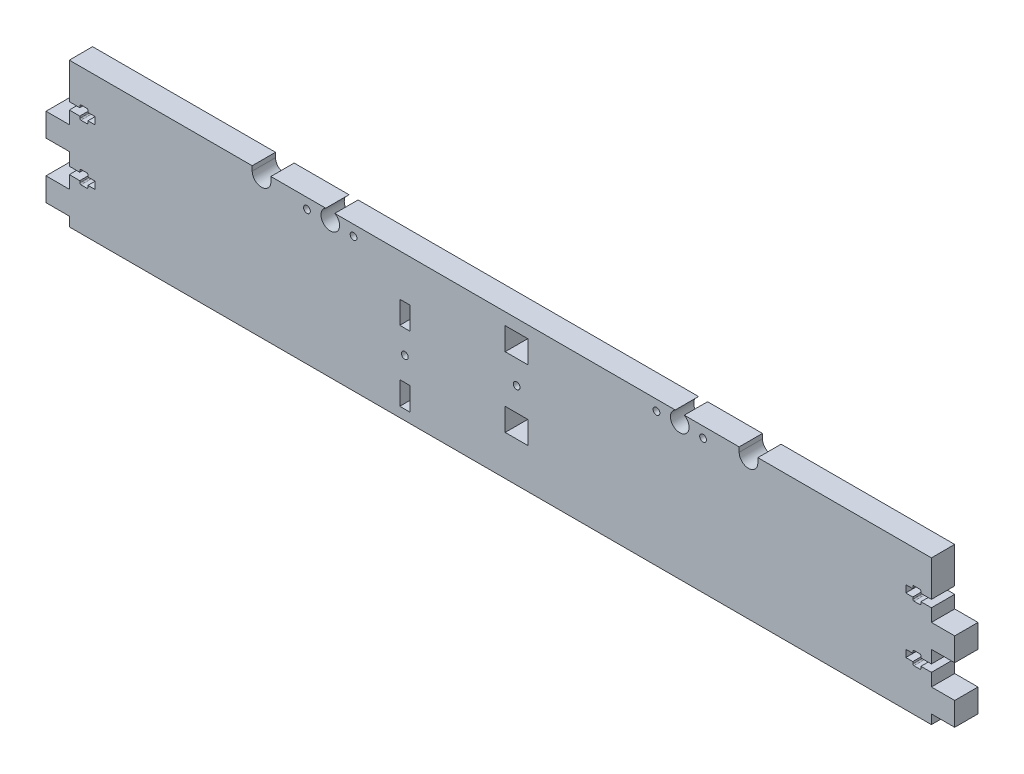
SolidWorks part; units mm, degrees
ref_plane "Front Plane" through (0, 0, 0) normal (0, 0, 1) x (1, 0, 0)
ref_plane "Top Plane" through (0, 0, 0) normal (0, 1, 0) x (1, 0, 0)
ref_plane "Right Plane" through (0, 0, 0) normal (1, 0, 0) x (0, 0, -1)
sketch "Sketch1" plane through (0, 0, 0) normal (0, 0, 1) x (1, 0, 0)
  line L0 (0, 0) -> (-185, 0)
  line L1 (-185, 0) -> (-185, -62) construction
  line L2 (0, -62) -> (-185, -62)
  line L3 (-185, -62) -> (-185, -58)
  line L4 (-185, -58) -> (-195, -58)
  line L5 (-195, -58) -> (-195, -48)
  line L6 (-195, -48) -> (-185, -48)
  line L7 (-185, -48) -> (-185, -34)
  line L8 (-185, -34) -> (-195, -34)
  line L9 (-195, -34) -> (-195, -24)
  line L10 (-195, -24) -> (-185, -24)
  line L11 (0, -62) -> (0, 0)
  line L12 (-185, -24) -> (-185, 0)
  line L13 (-195, -58) -> (-195, -24) construction
  line L14 (-195, -29) -> (-185, -29) construction
  line L15 (-195, -53) -> (-185, -53) construction
  dimension "D1" = 185
  dimension "D2" = 10
  dimension "D3" = 10
  dimension "D4" = 10
  dimension "D5" = 24
  dimension "D6" = 29
  dimension "D7" = 62
extrude "MainBody" add sketch "Sketch1" along normal blind 10
sketch "Sketch3" plane through (0, 0, 10) normal (0, 0, 1) x (1, 0, 0)
  line L0 (-185, -17) -> (-174, -17) construction
  line L1 (-185, 0) -> (-185, -24) construction
  line L2 (-185, -18.55) -> (-180.5, -18.55)
  line L3 (-180.5, -18.55) -> (-180.5, -19.35)
  line L4 (-180, -19.85) -> (-177.5, -19.85)
  line L5 (-177, -19.35) -> (-177, -18.55)
  line L6 (-177, -18.55) -> (-174, -18.55)
  line L7 (-174, -18.55) -> (-174, -15.45)
  line L8 (-180.5, -18.55) -> (-177, -18.55) construction
  line L9 (-195, -24) -> (-195, -34) construction
  line L10 (-180.5, -15.45) -> (-177, -15.45) construction
  line L11 (-177, -15.45) -> (-174, -15.45)
  line L12 (-177, -14.65) -> (-177, -15.45)
  line L13 (-180, -14.15) -> (-177.5, -14.15)
  line L14 (-180.5, -15.45) -> (-180.5, -14.65)
  line L15 (-185, -15.45) -> (-180.5, -15.45)
  line L16 (-185, -18.55) -> (-185, -15.45)
  line L17 (-185, -24) -> (-185, -34) construction
  line L19 (-195, -24) -> (-195, -34) construction
  line L20 (-195, -29) -> (-185, -29) construction
  line L21 (-180.5, -42.55) -> (-177, -42.55) construction
  line L22 (-180.5, -39.45) -> (-177, -39.45) construction
  line L23 (-185, -41) -> (-174, -41) construction
  line L24 (-185, -39.45) -> (-185, -42.55)
  line L25 (-185, -42.55) -> (-180.5, -42.55)
  line L26 (-180.5, -42.55) -> (-180.5, -43.35)
  line L27 (-180, -43.85) -> (-177.5, -43.85)
  line L28 (-177, -43.35) -> (-177, -42.55)
  line L29 (-177, -42.55) -> (-174, -42.55)
  line L30 (-174, -39.45) -> (-174, -42.55)
  line L31 (-177, -39.45) -> (-174, -39.45)
  line L32 (-177, -38.65) -> (-177, -39.45)
  line L33 (-180, -38.15) -> (-177.5, -38.15)
  line L34 (-180.5, -39.45) -> (-180.5, -38.65)
  line L35 (-185, -39.45) -> (-180.5, -39.45)
  line L36 (-180.5, -15.45) -> (-177, -15.45) construction
  arc A0 (-177.5, -19.85) -> (-177, -19.35) centre (-177.5, -19.35) ccw
  arc A1 (-180.5, -19.35) -> (-180, -19.85) centre (-180, -19.35) ccw
  arc A2 (-180.5, -14.65) -> (-180, -14.15) centre (-180, -14.65) cw
  arc A3 (-177.5, -14.15) -> (-177, -14.65) centre (-177.5, -14.65) cw
  arc A4 (-177.5, -43.85) -> (-177, -43.35) centre (-177.5, -43.35) ccw
  arc A5 (-180.5, -43.35) -> (-180, -43.85) centre (-180, -43.35) ccw
  arc A6 (-180.5, -38.65) -> (-180, -38.15) centre (-180, -38.65) cw
  arc A7 (-177.5, -38.15) -> (-177, -38.65) centre (-177.5, -38.65) cw
  point P6 (-195, -29)
  point P15 (-177, -19.85)
  point P18 (-180.5, -19.85)
  point P29 (-180.5, -14.15)
  point P30 (-177, -14.15)
  point P62 (-177, -43.85)
  point P63 (-180.5, -43.85)
  point P64 (-180.5, -38.15)
  point P65 (-177, -38.15)
  dimension "D2" = 8
  dimension "D7" = 0.5
  dimension "D1" = 11
  dimension "D3" = 1.55
  dimension "D4" = 2.85
  dimension "D5" = 12
  dimension "D6" = 3.5
extrude "ScrewCutouts" cut sketch "Sketch3" against normal through all
mirror "Mirror1" about plane through (0, 0, 0) normal (1, 0, 0) of "ScrewCutouts", "MainBody"
sketch "Sketch2" plane through (0, 0, 10) normal (0, 0, 1) x (1, 0, 0)
  line L0 (0, 0) -> (0, -62) construction
  line L1 (-185, -62) -> (185, -62) construction
  line L2 (2, 0) -> (2, -62) construction
  line L3 (185, 0) -> (-185, 0) construction
  line L4 (-63, -4.5) -> (-83, -4.5) construction
  line L5 (-73, -7.5) -> (-73, 0.5) construction
  line L6 (77, -7.5) -> (77, 0.5) construction
  line L7 (67, -4.5) -> (87, -4.5) construction
  circle A0 centre (-73, -3.5) radius 4
  circle A1 centre (-83, -4.5) radius 1.45
  circle A2 centre (-63, -4.5) radius 1.45
  circle A3 centre (67, -4.5) radius 1.45
  circle A4 centre (87, -4.5) radius 1.45
  circle A5 centre (77, -3.5) radius 4
  dimension "D1" = 2.9
  dimension "D2" = 8
  dimension "D4" = 3.5
  dimension "D5" = 75
  dimension "D6" = 2
  dimension "D3" = 10
  dimension "D7" = 1
extrude "RodCutouts" cut sketch "Sketch2" against normal through all
sketch "Sketch4" plane through (0, 0, 10) normal (0, 0, 1) x (1, 0, 0)
  line L0 (77, -3.5) -> (-73, -3.5) construction
  line L1 (2, -3.5) -> (2, -62) construction
  line L2 (-185, -62) -> (185, -62) construction
  line L3 (7, -44.85) -> (7, -5.15) construction
  line L4 (75.0635, 0) -> (-71.0635, 0) construction
  line L5 (7, -10) -> (7, -40) construction
  line L6 (2.075, -5.15) -> (11.925, -5.15)
  line L7 (2.075, -5.15) -> (2.075, -14.85)
  line L8 (2.075, -14.85) -> (11.925, -14.85)
  line L9 (11.925, -5.15) -> (11.925, -14.85)
  line L10 (2.075, -5.15) -> (11.925, -14.85) construction
  line L11 (2.075, -14.85) -> (11.925, -5.15) construction
  line L12 (2.075, -35.15) -> (11.925, -35.15)
  line L13 (2.075, -35.15) -> (2.075, -44.85)
  line L14 (2.075, -44.85) -> (11.925, -44.85)
  line L15 (11.925, -35.15) -> (11.925, -44.85)
  line L16 (2.075, -35.15) -> (11.925, -44.85) construction
  line L17 (2.075, -44.85) -> (11.925, -35.15) construction
  circle A0 centre (7, -25) radius 1.45
  point P12 (7, -10)
  point P17 (7, -40)
  dimension "D8" = 2.9
  dimension "D1" = 9.85
  dimension "D2" = 9.7
  dimension "D3" = 9.85
  dimension "D4" = 9.7
  dimension "D5" = 30
  dimension "D6" = 10
  dimension "D7" = 5
extrude "Cut-Extrude3" cut sketch "Sketch4" against normal through all
sketch "Sketch5" plane through (0, 0, 10) normal (0, 0, 1) x (1, 0, 0)
  line L0 (-41, 0) -> (-41, -62) construction
  line L1 (-74.9365, 0) -> (-185, 0) construction
  line L2 (-185, -62) -> (185, -62) construction
  line L3 (-43.175, -27.65) -> (-43.175, -47.85) construction
  line L4 (-43.175, -17.95) -> (-38.825, -17.95)
  line L5 (-43.175, -17.95) -> (-43.175, -27.65)
  line L6 (-43.175, -27.65) -> (-38.825, -27.65)
  line L7 (-38.825, -17.95) -> (-38.825, -27.65)
  line L8 (-43.175, -17.95) -> (-38.825, -27.65) construction
  line L9 (-43.175, -27.65) -> (-38.825, -17.95) construction
  line L10 (-43.175, -47.85) -> (-38.825, -47.85)
  line L11 (-43.175, -47.85) -> (-43.175, -57.75)
  line L12 (-43.175, -57.75) -> (-38.825, -57.75)
  line L13 (-38.825, -47.85) -> (-38.825, -57.75)
  line L14 (-43.175, -47.85) -> (-38.825, -57.75) construction
  line L15 (-43.175, -57.75) -> (-38.825, -47.85) construction
  line L16 (-38.825, -47.85) -> (-38.825, -27.65) construction
  line L17 (-43.175, -37.75) -> (-38.825, -37.75) construction
  line L18 (-73, -3.5) -> (77, -3.5) construction
  line L19 (2, -3.5) -> (2, -62) construction
  line L20 (2, -32.75) -> (-195, -32.75) construction
  line L21 (-195, -24) -> (-195, -34) construction
  line L22 (-34.625, 8.9944) -> (-34.625, 5) construction
  line L23 (75.0635, 0) -> (-71.0635, 0) construction
  line L24 (-31.425, 8.9944) -> (-31.425, 5)
  line L25 (-37.825, 8.9944) -> (-37.825, 5)
  circle A0 centre (-41, -37.75) radius 1.45
  arc A1 (-31.425, 8.9944) -> (-37.825, 8.9944) centre (-34.625, 8.9944) ccw
  arc A2 (-37.825, 5) -> (-31.425, 5) centre (-34.625, 5) ccw
  point P6 (-41, -22.8)
  point P11 (-41, -52.8)
  point P34 (-34.625, 6.9972)
  dimension "D4" = 9.7
  dimension "D5" = 30
  dimension "D6" = 2.9
  dimension "D9" = 3.2
  dimension "D1" = 4.35
  dimension "D2" = 0
  dimension "D3" = 9.9
  dimension "D7" = 43
  dimension "D8" = 5
  dimension "D10" = 5
  dimension "D11" = 1
extrude "EndstopHolder" cut sketch "Sketch5" against normal through all
sketch "Sketch6" plane through (0, 0, 10) normal (0, 0, 1) x (1, 0, 0)
  line L0 (-43.175, -47.85) -> (-43.175, -27.65) construction
  line L1 (-42.35, -47.85) -> (-30.825, -47.85) construction
  line L3 (-30.825, -53.85) -> (-30.825, -41.85) construction
  line L4 (-32.825, -53.85) -> (-32.825, -41.85)
  line L5 (-28.825, -53.85) -> (-28.825, -41.85)
  line L6 (-38.825, -47.85) -> (-43.175, -47.85) construction
  line L7 (-38.825, -57.75) -> (-38.825, -47.85) construction
  arc A0 (-32.825, -53.85) -> (-28.825, -53.85) centre (-30.825, -53.85) ccw
  arc A1 (-28.825, -41.85) -> (-32.825, -41.85) centre (-30.825, -41.85) ccw
  point P10 (-30.825, -47.85)
  dimension "D1" = 2
  dimension "D2" = 12
  dimension "D3" = 8
  dimension "D4" = 0
extrude "EndstopWires" [suppressed] cut sketch "Sketch6" against normal through all
sketch "Sketch7" plane through (0, 0, 10) normal (0, 0, 1) x (1, 0, 0)
  line L0 (-73, -3.5) -> (77, -3.5) construction
  line L1 (2, -3.5) -> (2, -62) construction
  line L3 (-102.5, 0) -> (-102.5, -2) construction
  line L4 (-74.9365, 0) -> (-185, 0) construction
  line L5 (-98.5, 0) -> (-98.5, -2)
  line L6 (-106.5, 0) -> (-106.5, -2)
  line L7 (106.5, 0) -> (106.5, -2) construction
  line L8 (102.5, 0) -> (102.5, -2)
  line L9 (110.5, 0) -> (110.5, -2)
  line L10 (-185, -62) -> (185, -62) construction
  arc A0 (-98.5, 0) -> (-106.5, 0) centre (-102.5, 0) ccw
  arc A1 (-106.5, -2) -> (-98.5, -2) centre (-102.5, -2) ccw
  arc A2 (102.5, 0) -> (110.5, 0) centre (106.5, 0) cw
  arc A3 (110.5, -2) -> (102.5, -2) centre (106.5, -2) cw
  point P12 (-102.5, -1)
  point P19 (106.5, -1)
  dimension "D3" = 4
  dimension "D1" = 2
  dimension "D2" = 104.5
extrude "Cut-Extrude4" cut sketch "Sketch7" against normal through all
equation "\"Y-ROD-SPACING\"=75"
equation "\"D5@Sketch2\"=\"Y-ROD-SPACING\""
equation "\"Y-BED-OFFSET\"=2"
equation "\"D6@Sketch2\"=\"Y-BED-OFFSET\""
equation "\"T-SLOT-NUT-FILLET-RADIUS\"=0.5"
equation "\"D7@Sketch3\"=\"T-SLOT-NUT-FILLET-RADIUS\""
equation "\"T-SLOT-SCREW-SHAFT-RADIUS\"=1.55"
equation "\"D3@Sketch3\"=\"T-SLOT-SCREW-SHAFT-RADIUS\""
equation "\"T-SLOT-SCREW-SHAFT-CUTOUT-LENGTH\"=11"
equation "\"D1@Sketch3\"=\"T-SLOT-SCREW-SHAFT-CUTOUT-LENGTH\""
equation "\"T-SLOT-NUT-DEPTH\"=3.5"
equation "\"D6@Sketch3\"=\"T-SLOT-NUT-DEPTH\""
equation "\"T-SLOT-NUT-WIDTH\"=2.85"
equation "\"D4@Sketch3\"=\"T-SLOT-NUT-WIDTH\""
equation "\"T-SLOT-NUT-END-DISTANCE\"=8"
equation "\"D2@Sketch3\"=\"T-SLOT-NUT-END-DISTANCE\""
equation "\"ACRYLIC-TAB-CUTOUT-SIZE\"=\"ACRYLIC-THICKNESS\"+\"ACRYLIC-TAB-TOLERANCE\"*2"
equation "\"D1@Sketch4\"=\"ACRYLIC-THICKNESS\"-\"KERF\"*2"
equation "\"D2@Sketch4\"=\"ACRYLIC-TAB-WIDTH\"-\"KERF\"*4"
equation "\"D3@Sketch4\"=\"ACRYLIC-THICKNESS\"-\"KERF\"*2"
equation "\"D4@Sketch4\"=\"ACRYLIC-TAB-WIDTH\"-\"KERF\"*4"
equation "\"ACRYLIC-M3-HOLE\"=2.9"
equation "\"D8@Sketch4\"=\"ACRYLIC-M3-HOLE\""
equation "\"Y-BED-ROD-INSET\"=3.5"
equation "\"D1@Sketch2\"=\"ACRYLIC-M3-HOLE\""
equation "\"D4@Sketch2\"=\"Y-BED-ROD-INSET\""
equation "\"SMOOTHROD-CAP-SCREW-DISTANCE\"=20"
equation "\"D3@Sketch2\"=\"SMOOTHROD-CAP-SCREW-DISTANCE\"/2"
equation "\"ACRYLIC-TAB-WIDTH\"=\"ACRYLIC-THICKNESS\""
equation "\"FRAME-WIDTH-INNER\"=370"
equation "\"D2@Sketch1\"=\"ACRYLIC-TAB-WIDTH\""
equation "\"D3@Sketch1\"=\"ACRYLIC-TAB-WIDTH\""
equation "\"D4@Sketch1\"=\"ACRYLIC-TAB-WIDTH\""
equation "\"D1@Sketch1\"=\"FRAME-WIDTH-INNER\"/2"
equation "\"X-ROD-SPACING\"=45"
equation "\"Z-ROD-SPACING\"=17.5"
equation "\"ACRYLIC-THICKNESS\"=10"
equation "\"ACRYLIC-THICKNESS2\"=4.5"
equation "\"NEMA17-HOLE-SPACING\"=31"
equation "\"NEMA17-CENTRAL-CUTOUT\"=22.5"
equation "\"Z-BRACKET-REACH\"=55"
equation "\"TOP-BRACKET-SPACING\"=40"
equation "\"SMOOTHROD-X-LENGTH\"=350"
equation "\"SMOOTHROD-Y-LENGTH\"=350"
equation "\"SMOOTHROD-Z-LENGTH\"=350"
equation "\"SMOOTHROD-TIGHTENING-HEADROOM\"=.25"
equation "\"LEADSCREW-Z-LENGTH\"=300"
equation "\"SCREW-LENGTH-FRAME\"=\"ACRYLIC-THICKNESS\" + 10"
equation "\"SCREW-HEAD-RADIUS\"=6"
equation "\"PRINTED-X-SMOOTHROD-DIAMETER\"=8.8"
equation "\"PRINTED-X-SMOOTHROD-CUTOUT\"=10"
equation "\"PRINTED-X-BASE-HEIGHT\"=10"
equation "\"PRINTED-LM8UU-CUTOUT-SIZE\"=15.5"
equation "\"PRINTED-LM8UU-CUTOUT-LENGTH\"=24.5"
equation "\"PRINTED-X-IDLER-HEIGHT\"=16"
equation "\"PSU-MOUNTING-WIDTH\"=95"
equation "\"PSU-MOUNTING-HEIGHT\"=177"
equation "\"D1@MainBody\"=\"ACRYLIC-THICKNESS\""
equation "\"D1@Sketch5\"=\"ACRYLIC-THICKNESS2\"-\"KERF\"*2"
equation "\"D3@Sketch5\"=\"ACRYLIC-TAB-CUTOUT-SIZE\""
equation "\"D4@Sketch5\"=\"ACRYLIC-TAB-WIDTH\"-\"KERF\"*4"
equation "\"D6@Sketch5\"=\"ACRYLIC-M3-HOLE\""
equation "\"Y-BED-SCREW-SPACING\"=209"
equation "\"Y-BED-SCREW-CUTOUT-SLOT-HEIGHT\"=2"
equation "\"Z-ROD-INSET\"=13.5"
equation "\"Y-BELT-TO-ROD-DISTANCE\"=20"
equation "\"SPOOL-HOLDER-ROD-SPACING\"=150"
equation "\"D1@Sketch7\"=\"Y-BED-SCREW-CUTOUT-SLOT-HEIGHT\""
equation "\"D2@Sketch7\"=\"Y-BED-SCREW-SPACING\"/2"
equation "\"ACRYLIC-TAB-TOLERANCE\"=-.05"
equation "\"SCREW-LENGTH-MOTOR\"=\"ACRYLIC-THICKNESS\" + 5"
equation "\"SCREW-LENGTH-EXTRUDER\"=28"
equation "\"ACRYLIC-X-CARRIAGE-WIDTH\"=55"
equation "\"ACRYLIC-X-CARRIAGE-HEIGHT\"=75"
equation "\"ACRYLIC-X-CARRIAGE-LM8UU-CUTOUT-WIDTH\"=24.25"
equation "\"ACRYLIC-X-CARRIAGE-SCREW-SPACING-X\"=15"
equation "\"ACRYLIC-X-CARRIAGE-SCREW-SPACING-Y\"=33"
equation "\"ACRYLIC-X-CARRIAGE-CENTER-TAB-SPACING\"=14"
equation "\"ACRYLIC-X-CARRIAGE-EXTRUDER-OFFSET\"=26"
equation "\"ACRYLIC-X-CARRIAGE-EXTRUDER-ANGLE\"=90"
equation "\"ACRYLIC-X-CARRIAGE-EXTRUDER-SHELF-DEPTH\"=\"ACRYLIC-X-CARRIAGE-EXTRUDER-OFFSET\" + 28"
equation "\"ACRYLIC-X-CARRIAGE-EXTRUDER-BRACE-SPACING\"=23"
equation "\"ACRYLIC-X-CARRIAGE-EXTRUDER-BRACE-TAB-OFFSET\"=20"
equation "\"ACRYLIC-X-CARRIAGE-EXTRUDER-BRACE-HEIGHT\"=35"
equation "\"ACRYLIC-X-CARRIAGE-EXTRUDER-BRACE-SCREW-SPACING\"=22"
equation "\"PRINTED-M3-HOLE\"=3.5"
equation "\"ACRYLIC-X-CARRIAGE-LM8UU-CUTOUT-HEIGHT\"=11.0"
equation "\"ACRYLIC-X-CARRIAGE-DUAL-WIDTH-MULTIPLIER\"=1.65"
equation "\"ACRYLIC-X-CARRIAGE-DUAL-HOTEND-SPACING\"=42"
equation "\"ACRYLIC-X-CARRIAGE-DUAL-WIDTH\"=75"
equation "\"ACRYLIC-X-CARRIAGE-DUAL-HOTEND-SEPARATION\"=36"
equation "\"ACRYLIC-X-CARRIAGE-DUAL-MOUNT-PLATE-DEPTH\"=75"
equation "\"ACRYLIC-X-CARRIAGE-DUAL-MOUNT-BRACE-WIDTH\"=33"
equation "\"ACRYLIC-X-CARRIAGE-DUAL-MOUNT-SCREW-WIDTH\"=40"
equation "\"BLOWER-FAN-WIDTH\"=15"
equation "\"KERF\"=0.075"
equation "\"PRINTED-M3-NUT-AF\"=6.25"
equation "\"ACRYLIC-X-CARRIAGE-DUAL-FAN-OFFSET\"=52"
equation "\"ACRYLIC-X-CARRIAGE-DUAL-FAN-HEIGHT\"=20"
